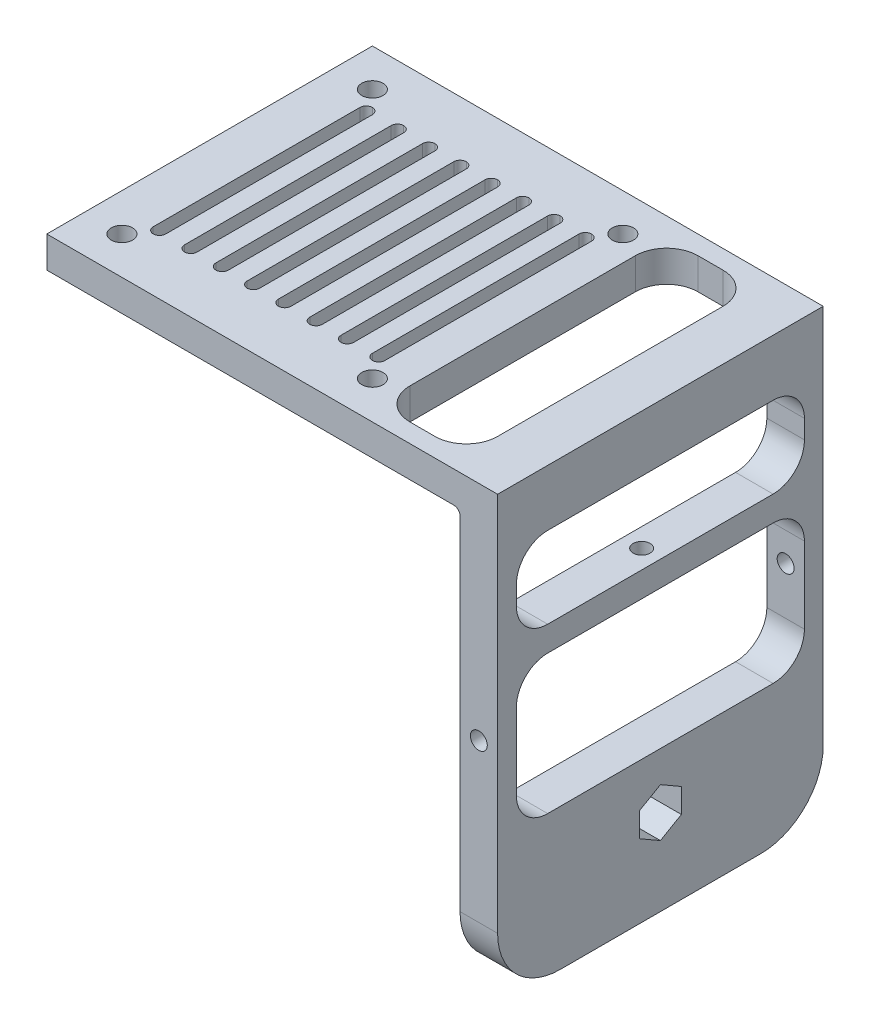
SolidWorks part; units mm, degrees
ref_plane "Front Plane" through (0, 0, 0) normal (0, 0, 1) x (1, 0, 0)
ref_plane "Top Plane" through (0, 0, 0) normal (0, 1, 0) x (1, 0, 0)
ref_plane "Right Plane" through (0, 0, 0) normal (1, 0, 0) x (0, 0, -1)
sketch "Sketch1" plane through (0, 0, 0) normal (0, 1, 0) x (1, 0, 0)
  line L0 (6, 46) -> (6, 6) construction
  line L1 (0, 0) -> (66, 0)
  line L2 (0, 0) -> (0, 52)
  line L3 (0, 52) -> (66, 52)
  line L4 (66, 0) -> (66, 52)
  line L5 (6, 6) -> (46, 6) construction
  line L6 (46, 6) -> (46, 46) construction
  line L7 (46, 46) -> (6, 46) construction
  circle A0 centre (6, 46) radius 1.7
  circle A1 centre (46, 46) radius 1.7
  circle A2 centre (46, 6) radius 1.7
  circle A3 centre (6, 6) radius 1.7
  dimension "D5" = 3.4
  dimension "D6" = 3.4
  dimension "D7" = 3.4
  dimension "D8" = 3.4
  dimension "D1" = 6
  dimension "D2" = 20
  dimension "D3" = 6
  dimension "D4" = 6
  dimension "D9" = 40
  dimension "D10" = 40
extrude "Boss-Extrude1" add sketch "Sketch1" along normal blind 5
sketch "Sketch2" plane through (0, 5, 0) normal (0, 1, 0) x (1, 0, 0)
  line L0 (0, 0) -> (66, 0) construction
  line L1 (66, 52) -> (72, 52)
  line L2 (66, 52) -> (66, 0)
  line L3 (66, 0) -> (72, 0)
  line L4 (72, 52) -> (72, 0)
  dimension "D1" = 6
  dimension "D2" = 0
extrude "Boss-Extrude2" add sketch "Sketch2" against normal blind 100
sketch "Sketch5" plane through (0, 5, 0) normal (0, 1, 0) x (1, 0, 0)
  line L0 (0, 26) -> (72, 26) construction
  line L1 (7.5, 8.5) -> (9.5, 8.5)
  line L2 (7.5, 8.5) -> (7.5, 43.5)
  line L3 (7.5, 43.5) -> (9.5, 43.5)
  line L4 (9.5, 8.5) -> (9.5, 43.5)
  line L5 (0, 52) -> (0, 0) construction
  line L6 (72, 0) -> (72, 52) construction
  dimension "D1" = 17.5
  dimension "D2" = 35
  dimension "D3" = 7.5
  dimension "D4" = 2
extrude "Cut-Extrude4" cut sketch "Sketch5" against normal blind 10 contours L2 L3 L4 L1
fillet "Fillet1" radius 1 4 edges at (7.5, 2.5, -43.5) (9.5, 2.5, -43.5) (9.5, 2.5, -8.5) (7.5, 2.5, -8.5)
pattern_linear "LPattern1" count 8 spacing 5 along (1, 0, 0) of "Fillet1", "Cut-Extrude4"
sketch "Sketch6" plane through (66, 0, 0) normal (-1, 0, 0) x (0, 0, 1)
  line L0 (-52, -95) -> (-52, 0) construction
  line L1 (2.3191, -65.7279) -> (-52, -65.7279)
  line L2 (2.3191, -65.7279) -> (2.3191, -97.9677)
  line L3 (2.3191, -97.9677) -> (-52, -97.9677)
  line L4 (-52, -65.7279) -> (-52, -97.9677)
  line L5 (2.3191, -65.7279) -> (-52, -97.9677) construction
  line L6 (2.3191, -97.9677) -> (-52, -65.7279) construction
  line L7 (-52, -95) -> (0, -95) construction
  line L8 (0, -95) -> (0, 0) construction
  point P0 (-24.8405, -81.8478)
  dimension "D1" = 2.9677
  dimension "D2" = 2.3191
  dimension "D3" = 29.2721
extrude "Cut-Extrude5" cut sketch "Sketch6" against normal blind 10
sketch "Sketch7" plane through (0, 0, 0) normal (0, -1, 0) x (1, 0, 0)
  line L0 (55, -49) -> (59, -49)
  line L1 (64, -44) -> (64, -8)
  line L2 (59, -3) -> (55, -3)
  line L3 (50, -8) -> (50, -44)
  line L4 (66, -52) -> (0, -52) construction
  line L5 (0, 0) -> (66, 0) construction
  line L6 (66, 0) -> (66, -52) construction
  circle A0 centre (46, -46) radius 1.7 construction
  arc A1 (55, -3) -> (50, -8) centre (55, -8) ccw
  arc A2 (64, -8) -> (59, -3) centre (59, -8) ccw
  arc A3 (59, -49) -> (64, -44) centre (59, -44) ccw
  arc A4 (55, -49) -> (50, -44) centre (55, -44) cw
  dimension "D5" = 5
  dimension "D1" = 3
  dimension "D2" = 3
  dimension "D3" = 2
  dimension "D4" = 4
extrude "Cut-Extrude6" cut sketch "Sketch7" against normal blind 10
fillet "Fillet2" radius 10 2 edges at (69, -65.7279, 0) (69, -65.7279, -52)
sketch "Sketch9" plane through (66, 0, 0) normal (-1, 0, 0) x (0, 0, 1)
  line L0 (-26, 0) -> (-26, -65.7279) construction
  line L1 (0, 0) -> (-52, 0) construction
  line L2 (-10, -65.7279) -> (-42, -65.7279) construction
  line L3 (0, -55.7279) -> (0, 0) construction
  line L4 (-26, -55.8982) -> (-22.65, -53.9641)
  line L5 (-22.65, -53.9641) -> (-22.65, -50.0959)
  line L6 (-22.65, -50.0959) -> (-26, -48.1618)
  line L7 (-26, -48.1618) -> (-29.35, -50.0959)
  line L8 (-29.35, -50.0959) -> (-29.35, -53.9641)
  line L9 (-29.35, -53.9641) -> (-26, -55.8982)
  circle A0 centre (-26, -52.03) radius 3.35 construction
  dimension "D1" = 6.7
  dimension "D2" = 52.03
  dimension "D3" = 26
extrude "Cut-Extrude7" cut sketch "Sketch9" against normal blind 10
sketch "Sketch10" plane through (66, 0, 0) normal (-1, 0, 0) x (0, 0, 1)
  line L0 (-44, -20.9721) -> (-8, -20.9721)
  line L1 (-3, -25.9721) -> (-3, -38.1618)
  line L2 (-8, -43.1618) -> (-44, -43.1618)
  line L3 (-49, -38.1618) -> (-49, -25.9721)
  line L4 (0, -55.7279) -> (0, 0) construction
  line L5 (-52, -55.7279) -> (-52, 0) construction
  arc A0 (-3, -38.1618) -> (-8, -43.1618) centre (-8, -38.1618) cw
  arc A1 (-44, -43.1618) -> (-49, -38.1618) centre (-44, -38.1618) cw
  arc A2 (-44, -20.9721) -> (-49, -25.9721) centre (-44, -25.9721) ccw
  arc A3 (-8, -20.9721) -> (-3, -25.9721) centre (-8, -25.9721) cw
  dimension "D3" = 5
  dimension "D4" = 5
  dimension "D1" = 3
  dimension "D2" = 3
  dimension "D5" = 20.9721
extrude "Cut-Extrude8" cut sketch "Sketch10" against normal blind 10 contours L0 | L1 | L2 | L3 region at (66, -32.0669, -26)
fillet "Fillet3" radius 1 1 edges at (66, 0, -26)
sketch "Sketch11" plane through (0, 0, -52) normal (0, 0, -1) x (-1, 0, 0)
  line L2 (-72, 5) -> (0, 5) construction
  line L3 (-69, 5) -> (-69, -30.57) construction
  circle A0 centre (-69, -30.57) radius 1.35
  dimension "D1" = 2.7
extrude "Cut-Extrude9" cut sketch "Sketch11" against normal up to vertex (52 mm away) up to point (66, -1, 0)
sketch "Sketch13" plane through (0, -20.9721, 0) normal (0, -1, 0) x (1, 0, 0)
  line L0 (66, -26) -> (72, -26) construction
  line L1 (66, -44) -> (66, -8) construction
  line L2 (72, -8) -> (72, -44) construction
  circle A0 centre (69, -26) radius 1.35
  dimension "D1" = 2.7
extrude "Cut-Extrude11" cut sketch "Sketch13" against normal blind 10
sketch "Sketch15" plane through (66, 0, 0) normal (-1, 0, 0) x (0, 0, 1)
  line L4 (-3, -11.9721) -> (-3, -9)
  line L5 (-8, -4) -> (-44, -4)
  line L6 (-49, -9) -> (-49, -11.9721)
  line L7 (-44, -16.9721) -> (-8, -16.9721)
  line L8 (0, -55.7279) -> (0, -1) construction
  line L9 (-52, -55.7279) -> (-52, -1) construction
  line L10 (0, -1) -> (-52, -1) construction
  line L11 (-44, -20.9721) -> (-8, -20.9721) construction
  arc A2 (-49, -11.9721) -> (-44, -16.9721) centre (-44, -11.9721) ccw
  arc A3 (-44, -4) -> (-49, -9) centre (-44, -9) ccw
  arc A4 (-3, -9) -> (-8, -4) centre (-8, -9) ccw
  arc A5 (-3, -11.9721) -> (-8, -16.9721) centre (-8, -11.9721) cw
  point P11 (-26, -1)
  dimension "D5" = 5
  dimension "D1" = 3
  dimension "D2" = 3
  dimension "D3" = 3
  dimension "D4" = 4
extrude "Cut-Extrude12" cut sketch "Sketch15" against normal blind 10
